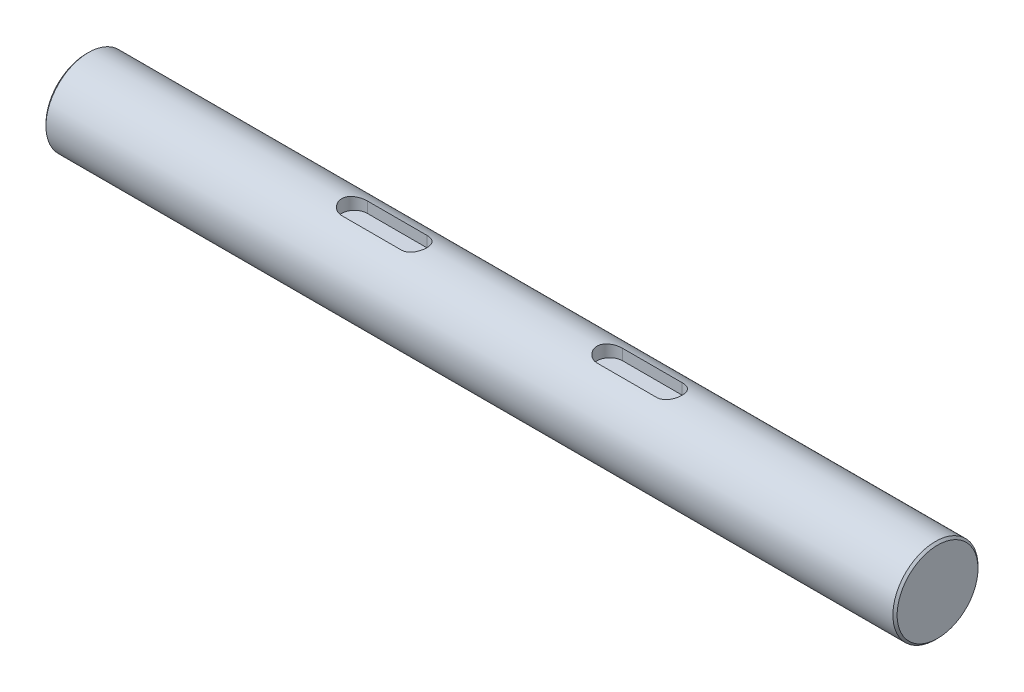
SolidWorks part; units mm, degrees
material "45"
ref_plane "前视基准面" through (0, 0, 0) normal (0, 0, 1) x (1, 0, 0)
ref_plane "上视基准面" through (0, 0, 0) normal (0, 1, 0) x (1, 0, 0)
ref_plane "右视基准面" through (0, 0, 0) normal (1, 0, 0) x (0, 0, -1)
ref_axis "基准轴1" through (88.99, 0, 0) along (-1, 0, 0)
sketch "草图1" plane through (0, 0, 0) normal (1, 0, 0) x (0, 0, -1)
  circle A0 centre (0, 0) radius 10
extrude "凸台-拉伸1" add sketch "草图1" along normal blind 100
ref_plane "基准面1" through (0, 10, 0) normal (0, 1, 0) x (1, 0, 0)
sketch "草图2" plane through (0, 10, 0) normal (0, 1, 0) x (1, 0, 0)
  line L0 (63, 3) -> (77, 3)
  line L1 (63, -3) -> (77, -3)
  arc A0 (63, 3) -> (63, -3) centre (63, 0) ccw
  arc A1 (77, 3) -> (77, -3) centre (77, 0) cw
  dimension "D1" = 3
  dimension "D2" = 14
extrude "切除-拉伸1" cut sketch "草图2" against normal blind 3
chamfer "倒角1" distance 0.5 angle 45 1 edges at (0, 0, -10)
sketch "草图3" plane through (100, 0, 0) normal (1, 0, 0) x (0, 0, -1)
  circle A0 centre (0, 0) radius 10
extrude "凸台-拉伸2" add sketch "草图3" along normal blind 100
ref_plane "基准面2" through (0, 10, 0) normal (0, 1, 0) x (1, 0, 0)
sketch "草图4" plane through (0, 10, 0) normal (0, 1, 0) x (1, 0, 0)
  line L0 (123, 3) -> (137, 3)
  line L1 (123, -3) -> (137, -3)
  arc A0 (123, 3) -> (123, -3) centre (123, 0) ccw
  arc A1 (137, 3) -> (137, -3) centre (137, 0) cw
  dimension "D1" = 3
  dimension "D2" = 14
extrude "切除-拉伸2" cut sketch "草图4" against normal blind 3
chamfer "倒角2" distance 0.5 angle 45 1 edges at (200, 0, -10)
